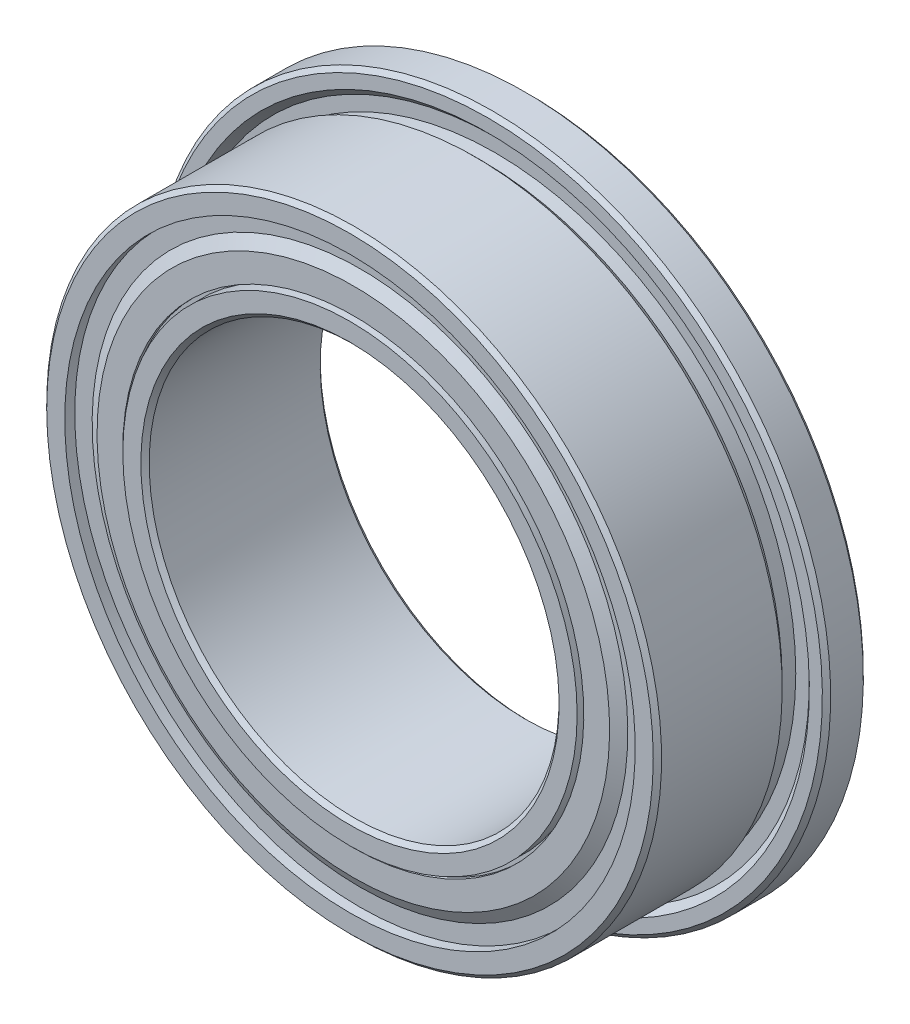
SolidWorks part; units mm, degrees
ref_plane "Front Plane" through (0, 0, 0) normal (0, 0, 1) x (1, 0, 0)
ref_plane "Top Plane" through (0, 0, 0) normal (0, 1, 0) x (1, 0, 0)
ref_plane "Right Plane" through (0, 0, 0) normal (1, 0, 0) x (0, 0, -1)
sketch "Sketch1" plane through (0, 0, 0) normal (1, 0, 0) x (0, 0, -1)
  line L0 (0, 6) -> (0, -6) construction
  line L1 (-1.75, 6) -> (1.75, 6) construction
  line L2 (0, 0) -> (1.75, 0) construction
  line L3 (1.75, 6.6) -> (1.75, -6.6) construction
  line L4 (1.75, -6.6) -> (0.95, -6.6) construction
  line L5 (1.75, 4) -> (0, 4) construction
  line L6 (1.75, 4) -> (1.75, -4) construction
  dimension "OD" = 12
  dimension "Width" = 3.5
  dimension "Flange Thickness" = 0.8
  dimension "ID" = 8
  dimension "Flange OD" = 13.2
sketch "Sketch2" plane through (0, 0, 0) normal (1, 0, 0) x (0, 0, -1)
  line L0 (1.75, 6.6) -> (0.95, 6.6)
  line L1 (0.95, 6.6) -> (0.95, 6.2652)
  line L2 (0.6848, 6) -> (-1.75, 6)
  line L3 (-1.75, 6) -> (-1.75, 5.35)
  line L4 (-1.75, 5.35) -> (-0.4873, 5.35)
  line L5 (1.75, 6.6) -> (1.75, -6.6) construction
  line L6 (1.75, 5.35) -> (1.75, 6.6)
  line L7 (1.75, 4) -> (-1.75, 4)
  line L8 (-1.75, 4) -> (-1.75, 4.65)
  line L9 (-1.75, 4.65) -> (-0.4873, 4.65)
  line L10 (1.75, 4.65) -> (1.75, 4)
  line L11 (0, 6) -> (0, 4) construction
  line L12 (-0.6, 5) -> (0.6, 5) construction
  line L13 (0.4873, 5.35) -> (1.75, 5.35)
  line L14 (0.4873, 4.65) -> (1.75, 4.65)
  line L15 (0.95, 6.2652) -> (1.0826, 6.1326)
  line L16 (1.0826, 6.1326) -> (1.0826, 5.8674)
  line L17 (1.0826, 5.8674) -> (0.8174, 5.8674)
  line L18 (0.8174, 5.8674) -> (0.6848, 6)
  line L19 (0.95, 6) -> (1.0826, 5.8674) construction
  line L20 (1.0826, 6.1326) -> (0.8174, 5.8674) construction
  line L21 (0.6848, 6) -> (0.95, 6) construction
  line L22 (0.95, 6) -> (0.95, 6.2652) construction
  line L23 (-1.75, 0) -> (1.75, 0) construction
  circle A0 centre (0, 5) radius 0.6 construction
  arc A1 (-0.4873, 5.35) -> (0.4873, 5.35) centre (0, 5) cw
  arc A2 (-0.4873, 4.65) -> (0.4873, 4.65) centre (0, 5) ccw
  dimension "Ball Dia." = 1.2
  dimension "D2" = 135
  dimension "D3" = 0.375
  dimension "Race Thikness" = 0.65
  dimension "D4" = 0.7
revolve "Revolve1" add sketch "Sketch2" angle 360 about L2
fillet "Fillet1" radius 0.0813 3 edges at (0, -6.6, -1.75) (0, -6.6, -0.95) (0, -6, 1.75) profile chamfer
sketch "Sketch3" plane through (0, 0, 0) normal (0, 0, 1) x (1, 0, 0)
  line L0 (-4, 0) -> (4, 0) construction
  line L1 (-6, 0) -> (6, 0) construction
  point P5 (0, 0)
  dimension "ID2" = 8
  dimension "OD2" = 12
fillet "Fillet2" radius 0.0813 2 edges at (0, -4, -1.75) (0, -4, 1.75) profile chamfer
sketch "Sketch7" plane through (0, 0, 0) normal (0, 0, 1) x (1, 0, 0)
  line L0 (0, 5.6) -> (0, 4.4)
  line L1 (0, 6.6) -> (0, -6.6) construction
  line L2 (-0.6769, 5.6) -> (0, 0) construction
  line L3 (0, 0) -> (0.6769, 5.6) construction
  line L4 (0.6769, 5.6) -> (-0.6769, 5.6) construction
  circle A0 centre (0, 5) radius 0.6 construction
  circle A1 centre (0, 0) radius 5.6 construction
  circle A2 centre (0, 0) radius 4.4 construction
  arc A4 (0, 5.6) -> (0, 4.4) centre (0, 5) ccw
  dimension "D1" = 13.784
revolve "Revolve3" add sketch "Sketch7" angle 360 about L0
pattern_circular "CirPattern3" count 22 over 360 about axis through (0, 0, 0) along (0, 0, -1) of bodies 107
sketch "Sketch8" plane through (0, 0, 0) normal (1, 0, 0) x (0, 0, -1)
  line L1 (-1.75, 5.35) -> (-1.49, 5.35)
  line L2 (-1.75, 5.35) -> (-1.75, 5.5667)
  line L3 (-1.75, 5.5667) -> (-1.49, 5.5667)
  line L4 (-1.49, 5.35) -> (-1.49, 5.5667)
  line L5 (1.75, 5.35) -> (1.49, 5.35)
  line L6 (1.75, 5.35) -> (1.75, 5.5667)
  line L7 (1.75, 5.5667) -> (1.49, 5.5667)
  line L8 (1.49, 5.35) -> (1.49, 5.5667)
  line L9 (1.75, 4.65) -> (1.49, 4.65)
  line L10 (1.75, 4.65) -> (1.75, 4.4333)
  line L11 (1.75, 4.4333) -> (1.49, 4.4333)
  line L12 (1.49, 4.65) -> (1.49, 4.4333)
  line L13 (-1.75, 4.65) -> (-1.49, 4.65)
  line L14 (-1.75, 4.65) -> (-1.75, 4.4333)
  line L15 (-1.75, 4.4333) -> (-1.49, 4.4333)
  line L16 (-1.49, 4.65) -> (-1.49, 4.4333)
  dimension "D1" = 0.2167
  dimension "D2" = 0.26
revolve "Cut-Revolve1" cut sketch "Sketch8" angle 360 about L2
sketch "Sketch9" plane through (0, 0, 0) normal (1, 0, 0) x (0, 0, -1)
  line L0 (-1.49, 5.5667) -> (-1.49, 5.2095)
  line L1 (-1.49, 5.2095) -> (-1.62, 4.9844)
  line L2 (-1.62, 4.9844) -> (-1.62, 4.4983)
  line L3 (1.62, 4.4983) -> (1.62, 4.4333) construction
  line L4 (1.49, 5.5667) -> (1.49, 5.2095)
  line L5 (1.49, 5.2095) -> (1.62, 4.9844)
  line L6 (1.62, 4.9844) -> (1.62, 4.4983)
  line L7 (1.75, 4.4333) -> (1.49, 4.4333) construction
  line L8 (-1.555, 5.5667) -> (-1.555, 5.2269)
  line L9 (-1.555, 5.2269) -> (-1.685, 5.0018)
  line L10 (-1.685, 5.0018) -> (-1.685, 4.4983)
  line L11 (-1.49, 5.5667) -> (-1.555, 5.5667)
  line L12 (-1.62, 4.4983) -> (-1.685, 4.4983)
  line L13 (1.555, 5.5667) -> (1.555, 5.2269)
  line L14 (1.555, 5.2269) -> (1.685, 5.0018)
  line L15 (1.685, 5.0018) -> (1.685, 4.4983)
  line L16 (1.49, 5.5667) -> (1.555, 5.5667)
  line L17 (1.62, 4.4983) -> (1.685, 4.4983)
  line L18 (-1.49, 5.2095) -> (-1.49, 2.5308) construction
  line L19 (1.49, 5.2095) -> (1.49, 5.5667) construction
  line L20 (-1.49, 4.4333) -> (-1.75, 4.4333) construction
  line L22 (-1.62, 4.4983) -> (-1.62, 4.4333) construction
  dimension "D2" = 150
  dimension "D1" = 150
  dimension "D5" = 0.26
  dimension "D3" = 0.065
  dimension "D4" = 0.065
  dimension "D6" = 0.3571
revolve "Revolve4" add sketch "Sketch9" angle 360 about L2
equation "\"D1@Fillet1\"=\"Race Thikness@Sketch2\"/8"
equation "\"ID2@Sketch3\" = \"ID@Sketch1\""
equation "\"OD2@Sketch3\" = \"OD@Sketch1\""
equation "\"D1@Fillet2\"=\"Race Thikness@Sketch2\"/8"
equation "\"D1@CirPattern3\"=360/\"D1@Sketch7\"-4"
equation "\"D1@Sketch8\"=\"Race Thikness@Sketch2\"/3"
equation "\"D2@Sketch8\"=\"Race Thikness@Sketch2\"/2.5"
equation "\"D3@Sketch9\"=\"D5@Sketch9\"/4"
equation "\"D4@Sketch9\"=\"D5@Sketch9\"/4"
equation "\"D1@Sketch9\"=\"D2@Sketch9\""
equation "\"Ball Dia.@Sketch2\" = \"D1@Sketch2\"*.5"
equation "\"D4@Sketch2\"=((\"OD@Sketch1\"-\"ID@Sketch1\")/2)*.35"
